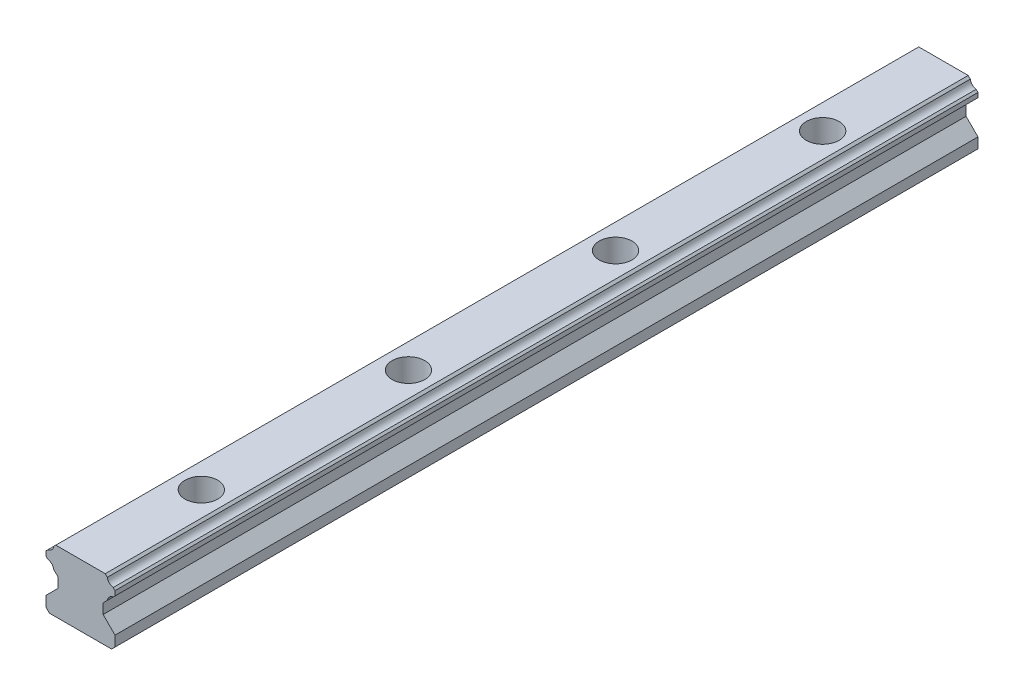
SolidWorks part; units mm, degrees
ref_plane "Front Plane" through (0, 0, 0) normal (0, 0, 1) x (1, 0, 0)
ref_plane "Top Plane" through (0, 0, 0) normal (0, 1, 0) x (1, 0, 0)
ref_plane "Right Plane" through (0, 0, 0) normal (1, 0, 0) x (0, 0, -1)
sketch "Sketch1" plane through (0, 0, 0) normal (0, 0, 1) x (1, 0, 0)
  line L0 (0, 13.3681) -> (0, -3.2505) construction
  line L1 (-6.55, 1.465) -> (-6.55, -1.465)
  line L2 (-6.55, 0) -> (0, 0) construction
  line L3 (-6.55, -1.465) -> (-10, -4.915)
  line L4 (-10, -4.915) -> (-10, -7.915)
  line L5 (-10, -7.915) -> (-9, -8.915)
  line L6 (-9, -8.915) -> (0, -8.915)
  line L7 (-6.55, 1.465) -> (-7.7681, 2.6831)
  line L8 (-10, 4.915) -> (-10, 6.245)
  line L9 (-10, 6.245) -> (-9.4697, 6.7753)
  line L10 (-7.16, 9.085) -> (0, 9.085)
  line L11 (-10, 4.915) -> (-10, -4.915) construction
  line L12 (-10, 5.58) -> (0, 5.58) construction
  line L13 (-7.7681, 8.4769) -> (-7.16, 9.085)
  line L14 (-9.4697, 4.3847) -> (-10, 4.915)
  line L15 (0, 9.085) -> (0, -8.915)
  arc A0 (-9.4697, 6.7753) -> (-7.7681, 8.4769) centre (-9.7486, 8.7558) ccw
  arc A1 (-9.4697, 4.3847) -> (-7.7681, 2.6831) centre (-9.7486, 2.4042) cw
  dimension "D10" = 4
  dimension "D1" = 2.93
  dimension "D2" = 6.55
  dimension "D3" = 9
  dimension "D4" = 7.16
  dimension "D5" = 3
  dimension "D6" = 1.33
  dimension "D7" = 18
  dimension "D8" = 45
  dimension "D9" = 45
  dimension "D11" = 0.75
  dimension "D12" = 0.86
extrude "Boss-Extrude1" add sketch "Sketch1" along normal blind 125
mirror "Mirror1" about plane through (0, 9.085, 125) normal (-1, 0, 0) of "Boss-Extrude1"
sketch "Sketch2" plane through (0, 9.085, 0) normal (0, 1, 0) x (1, 0, 0)
  line L0 (0, 130.187) -> (0, 31.9327) construction
  line L1 (7.16, 0) -> (-7.16, 0) construction
  circle A0 centre (0, -30) radius 3
  point P5 (0, -28.1112)
  dimension "D1" = 6
  dimension "D2" = 30
extrude "Cut-Extrude1" cut sketch "Sketch2" against normal through all
sketch "Sketch3" plane through (0, 9.085, 0) normal (0, 1, 0) x (1, 0, 0)
  circle A0 centre (0, -30) radius 4.75
  dimension "D1" = 9.5
extrude "Cut-Extrude2" cut sketch "Sketch3" against normal blind 8.5
pattern_linear "LPattern1" count 100 spacing 60 along (0, 0, 1) of "Cut-Extrude1", "Cut-Extrude2"
mirror "Mirror2" about plane through (-9.7486, 2.4042, 0) normal (0, 0, -1) of bodies 106
equation "\"length\"= 250mm"
equation "\"D1@Boss-Extrude1\"=\"length\" /2"
